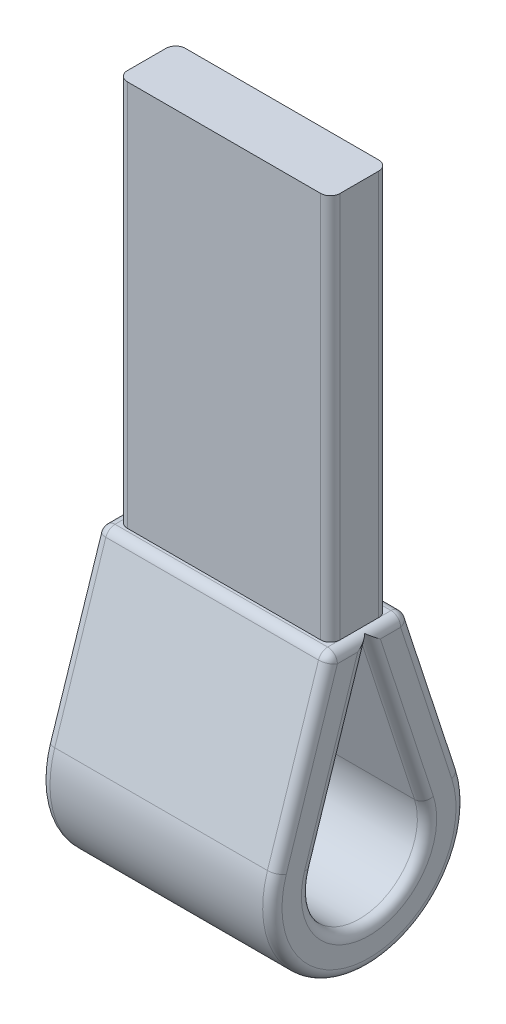
SolidWorks part; units mm, degrees
ref_plane "Front Plane" through (0, 0, 0) normal (0, 0, 1) x (1, 0, 0)
ref_plane "Top Plane" through (0, 0, 0) normal (0, 1, 0) x (1, 0, 0)
ref_plane "Right Plane" through (0, 0, 0) normal (1, 0, 0) x (0, 0, -1)
sketch "Sketch1" plane through (0, 0, 0) normal (1, 0, 0) x (0, 0, -1)
  line L0 (-5.7047, 1.8591) -> (0, 19.3647)
  line L1 (-9.5079, 3.0984) -> (-4, 20)
  line L2 (-4, 20) -> (-4, 60)
  line L3 (-4, 60) -> (4, 60)
  line L4 (4, 20) -> (4, 60)
  line L5 (-4, 20) -> (4, 20) construction
  line L6 (4, 20) -> (9.5079, 3.0984)
  line L7 (0, 19.3647) -> (5.7047, 1.8591)
  circle A0 centre (0, 0) radius 6 construction
  arc A1 (-9.5079, 3.0984) -> (9.5079, 3.0984) centre (0, 0) ccw
  arc A2 (-5.7047, 1.8591) -> (5.7047, 1.8591) centre (0, 0) ccw
  circle A3 centre (0, 0) radius 10 construction
  point P10 (10, 0)
  point P28 (0, -10)
  dimension "D1" = 12
  dimension "D3" = 8
  dimension "D4" = 30
  dimension "D5" = 40
  dimension "D2" = 4
extrude "Boss-Extrude1" add sketch "Sketch1" along normal blind 24
sketch "Sketch2" plane through (0, 60, 0) normal (0, 1, 0) x (1, 0, 0)
  line L4 (0, 4) -> (0, -4)
  line L5 (0, -4) -> (24, -4)
  line L6 (24, -4) -> (24, 4)
  line L7 (24, 4) -> (0, 4)
  line L8 (0, 4) -> (0, -4)
  line L9 (0, -4) -> (24, -4)
  line L10 (24, -4) -> (24, 4)
  line L11 (24, 4) -> (0, 4)
  line L16 (1, 3) -> (1, -3)
  line L17 (1, -3) -> (23, -3)
  line L18 (23, -3) -> (23, 3)
  line L19 (23, 3) -> (1, 3)
  line L20 (1, 3) -> (1, -3)
  line L21 (1, -3) -> (23, -3)
  line L22 (23, -3) -> (23, 3)
  line L23 (23, 3) -> (1, 3)
  dimension "D1" = 0
  dimension "D2" = 1
extrude "Cut-Extrude1" cut sketch "Sketch2" against normal up to vertex (40 mm away) up to point (0, 20, 4)
fillet "Fillet1" radius 1 16 edges at (24, 10.6119, -2.8524) (24, -6, 0) (24, 11.5492, -6.7539) (24, -10, 0) (0, 10.6119, 2.8524) (0, -6, 0) (0, 11.5492, -6.7539) (0, -10, 0) (24, 10.6119, 2.8524) (24, 20, 0) (24, 11.5492, 6.7539) (12, 20, -4) (12, 20, 4) (0, 10.6119, -2.8524) (0, 20, 0) (0, 11.5492, 6.7539)
fillet "Fillet2" radius 1 4 edges at (1, 40, -3) (1, 40, 3) (23, 40, -3) (23, 40, 3)
